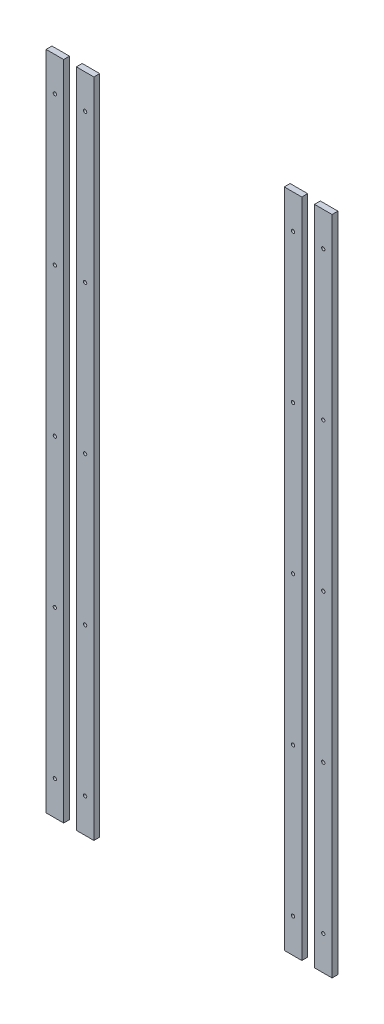
SolidWorks part; units mm, degrees
ref_plane "Спереди" through (0, 0, 0) normal (0, 0, 1) x (1, 0, 0)
ref_plane "Сверху" through (0, 0, 0) normal (0, 1, 0) x (1, 0, 0)
ref_plane "Справа" through (0, 0, 0) normal (1, 0, 0) x (0, 0, -1)
sketch "Четыре_направляющие_эскиз" plane through (0, 0, 0) normal (0, 0, 1) x (1, 0, 0)
  line L0 (325.5, -435) -> (343.5, -435)
  line L1 (343.5, -435) -> (343.5, 243)
  line L2 (343.5, 243) -> (325.5, 243)
  line L3 (325.5, 243) -> (325.5, -435)
  line L4 (356.5, -435) -> (374.5, -435)
  line L5 (374.5, -435) -> (374.5, 243)
  line L6 (374.5, 243) -> (356.5, 243)
  line L7 (356.5, 243) -> (356.5, -435)
  line L8 (569.7, -435) -> (587.7, -435)
  line L9 (587.7, -435) -> (587.7, 243)
  line L10 (587.7, 243) -> (569.7, 243)
  line L11 (569.7, 243) -> (569.7, -435)
  line L12 (600.7, -435) -> (618.7, -435)
  line L13 (618.7, -435) -> (618.7, 243)
  line L14 (618.7, 243) -> (600.7, 243)
  line L15 (600.7, 243) -> (600.7, -435)
  dimension "X001" = 325.5
  dimension "X002" = 343.5
  dimension "X003" = 356.5
  dimension "X004" = 374.5
  dimension "X005" = 569.7
  dimension "X006" = 587.7
  dimension "X007" = 600.7
  dimension "X008" = 618.7
  dimension "Y001" = 435
  dimension "Y002" = 243
extrude "Четыре_направляющие_6мм" add sketch "Четыре_направляющие_эскиз" along normal blind 6
sketch "Крепление_направляющих_М3_эскиз" plane through (0, 0, 0) normal (0, 0, 1) x (1, 0, 0)
  circle A0 centre (334.5, -400) radius 1.7
  circle A1 centre (365.5, -400) radius 1.7
  circle A2 centre (578.7, -400) radius 1.7
  circle A3 centre (609.7, -400) radius 1.7
  dimension "Диаметр001" = 3.4
  dimension "Диаметр002" = 3.4
  dimension "Диаметр003" = 3.4
  dimension "Диаметр004" = 3.4
  dimension "X001" = 334.5
  dimension "X002" = 365.5
  dimension "X003" = 578.7
  dimension "X004" = 609.7
  dimension "Y001" = 400
extrude "Проходы_направляющих_М3" cut sketch "Крепление_направляющих_М3_эскиз" against normal through all and the other way through all
pattern_linear "Массив_крепления_направляющих_5рядов" count 5 spacing 152 along (0, 1, 0) of "Проходы_направляющих_М3"
equation "\"Толщина стенки\" = \"Толщина тонких панелей\""
equation "\"Ширина груза\"= 160"
equation "\"Глубина груза\"= 240"
equation "\"Высота груза\"= 160"
equation "\"Ширина ячейки\"= \"Ширина груза\" + 10"
equation "\"Глубина ячейки\"= \"Глубина груза\" + 10"
equation "\"Высота ячейки\"= \"Высота груза\" + 10 + 13"
equation "\"Колво ячеек ширина\"= 2"
equation "\"Колво ячеек высота\"= 2"
equation "\"Крепление дверцы\"= 5 "
equation "\"Ширина рейки\"= \"Толщина шестерни\""
equation "\"Высота рейки\"= 20"
equation "\"Высота пола\" = 2*\"Толщина тонких панелей\""
equation "\"Колво полозьев\"= 5"
equation "\"Отступ рейки\"= 20"
equation "\"Глубина каретки\"= \"Глубина ячейки\" + 30 + \"Мотор Y высота корпуса\" + 20 + \"Удлинение платформы по глубине\""
equation "\"Длинна рейки\" = (\"Ширина ячейки\"+\"Толщина вертикальных стенок\"+\"Крепление дверцы\")*\"Колво ячеек ширина\"+\"Ширина ячейки выгрузки\"*\"Колво выгрузки\"+\"Толщина вертикальных стенок\"+2*\"Отступ крепления мотора фиксации\"-\"Крепление дверцы\"*\"Колво ячеек ширина\""
equation "\"Отступ шпильки\"= 26"
equation "\"Диаметр шпильки\"= 5"
equation "\"Длинна шпильки\" = (\"Высота ячейки\"+\"Толщина горизонтальных плит\"+\"Высота пола\")*\"Колво ячеек высота\"+2*(\"Толщина горизонтальных плит\"+\"Отступ рейки\")"
equation "\"Ширина пластины\" = 50"
equation "\"Высота зона выгрузки\"= \"Высота ячейки\" * 2 + \"Толщина стенки\" * 2"
equation "\"Колво выгрузки\"= 1"
equation "\"Ширина ячейки выгрузки\" = \"Ширина ячейки\"+\"Толщина вертикальных стенок\"+2*\"Отступ крепления мотора фиксации\""
equation "\"Отступ крепления мотора фиксации\" = (70-\"Толщина вертикальных стенок\")/2"
equation "\"Мотор X ширина корпуса\"= 42.3"
equation "\"Мотор X высота корпуса\"= 42.3"
equation "\"Мотор X длина корпуса\"= 40"
equation "\"Мотор X вылет вала\"= 19.8"
equation "\"Мотор Y ширина корпуса\"= 42.3"
equation "\"Мотор Y высота корпуса\"= 42.3"
equation "\"Мотор Y длина корпуса\"= 48"
equation "\"Мотор Y вылет вала\"= 30"
equation "\"Мотор Z ширина корпуса\"= 42"
equation "\"Мотор Z высота корпуса\"= 42"
equation "\"Мотор Z длина корпуса\"= 40"
equation "\"Мотор Z вылет вала\"= 23"
equation "\"Мотор диаметр вала ПРЕДВ\"= 5"
equation "\"Мотор шаг крепления ПРЕДВ\"= 31"
equation "\"Мотор диаметр отверстий ПРЕДВ\"= 3"
equation "\"Мотор глубина отверстий ПРЕДВ\"= 4.5"
equation "\"Мотор диаметр буртика ПРЕДВ\"= 22"
equation "\"Мотор высота буртика ПРЕДВ\"= 2"
equation "\"Мотор диаметр шкива ПРЕДВ\"= 16"
equation "\"Мотор длина шкива ПРЕДВ\"= 12"
equation "\"Мотор отступ шкива ПРЕДВ\"= 5"
equation "\"Мотор X шаг градусов\"= 1.8"
equation "\"Мотор Y шаг градусов\"= 1.8"
equation "\"Мотор Z шаг градусов\"= 1.8"
equation "\"Мотор Y диаметр ротора\"= 25.78"
equation "\"Толщина шестерни\"= 10"
equation "\"Толщина тонких панелей\" = 6"
equation "\"Толщина вертикальных стенок\" = 6"
equation "\"Толщина горизонтальных плит\" = 6"
equation "\"Базовая высота корпуса\"= (\"Высота ячейки\"+\"Толщина тонких панелей\"+\"Высота пола\")*\"Колво ячеек высота\"+6*\"Толщина тонких панелей\"+\"Мотор X ширина корпуса\"+\"Мотор Y ширина корпуса\"+75"
equation "\"Высота корпуса\"= (\"Высота ячейки\"+\"Толщина горизонтальных плит\"+\"Высота пола\")*\"Колво ячеек высота\"+2*\"Толщина горизонтальных плит\"+4*\"Толщина тонких панелей\"+\"Мотор X ширина корпуса\"+\"Мотор Y ширина корпуса\"+75"
equation "\"Смещение центра корпуса\"= (\"Высота корпуса\"-\"Базовая высота корпуса\")/2-(\"Толщина горизонтальных плит\"-\"Толщина тонких панелей\")"
equation "\"Отметка пола\"= -\"Базовая высота корпуса\"/2+\"Толщина тонких панелей\""
equation "\"Отметка потолка\"= \"Отметка пола\"+\"Высота корпуса\"-2*\"Толщина горизонтальных плит\""
equation "\"Отметка верхней полки\"= \"Отметка потолка\"-(28+\"Толщина тонких панелей\")-\"Высота ячейки\"-\"Высота пола\""
equation "\"Отметка нижней полки\"= \"Отметка верхней полки\"-\"Высота ячейки\"-\"Высота пола\"-\"Толщина горизонтальных плит\""
equation "\"Ширина направляющей\"= 18"
equation "\"X001@Четыре_направляющие_эскиз\" = \"Глубина ячейки\"+74.5-9+\"Смещение дальнего ряда под симметрию\""
equation "\"X002@Четыре_направляющие_эскиз\" = \"Глубина ячейки\"+74.5+9+\"Смещение дальнего ряда под симметрию\""
equation "\"X003@Четыре_направляющие_эскиз\" = \"Глубина ячейки\"+105.5-9+\"Смещение дальнего ряда под симметрию\""
equation "\"X004@Четыре_направляющие_эскиз\" = \"Глубина ячейки\"+105.5+9+\"Смещение дальнего ряда под симметрию\""
equation "\"X005@Четыре_направляющие_эскиз\" = (2*\"Глубина ячейки\"+46.8-9-\"Смещение пары направляющих от рейки\")+\"Удлинение платформы по глубине\""
equation "\"X006@Четыре_направляющие_эскиз\" = (2*\"Глубина ячейки\"+46.8+9-\"Смещение пары направляющих от рейки\")+\"Удлинение платформы по глубине\""
equation "\"X007@Четыре_направляющие_эскиз\" = (2*\"Глубина ячейки\"+77.8-9-\"Смещение пары направляющих от рейки\")+\"Удлинение платформы по глубине\""
equation "\"X008@Четыре_направляющие_эскиз\" = (2*\"Глубина ячейки\"+77.8+9-\"Смещение пары направляющих от рейки\")+\"Удлинение платформы по глубине\""
equation "\"Y001@Четыре_направляющие_эскиз\" = 2*\"Ширина ячейки\"+87+\"Расширение корпуса на сторону\"-2"
equation "\"Y002@Четыре_направляющие_эскиз\" = \"Ширина ячейки\"+65+\"Расширение корпуса на сторону\"-2"
equation "\"D1@Четыре_направляющие_6мм\" = \"Толщина тонких панелей\""
equation "\"X001@Крепление_направляющих_М3_эскиз\" = \"Глубина ячейки\"+74.5+\"Смещение дальнего ряда под симметрию\""
equation "\"X002@Крепление_направляющих_М3_эскиз\" = \"Глубина ячейки\"+105.5+\"Смещение дальнего ряда под симметрию\""
equation "\"X003@Крепление_направляющих_М3_эскиз\" = (2*\"Глубина ячейки\"+46.8-\"Смещение пары направляющих от рейки\")+\"Удлинение платформы по глубине\""
equation "\"X004@Крепление_направляющих_М3_эскиз\" = (2*\"Глубина ячейки\"+77.8-\"Смещение пары направляющих от рейки\")+\"Удлинение платформы по глубине\""
equation "\"Y001@Крепление_направляющих_М3_эскиз\" = (2*\"Ширина ячейки\"+87+\"Расширение корпуса на сторону\"-2)-35"
equation "\"Диаметр001@Крепление_направляющих_М3_эскиз\" = 3.4"
equation "\"Диаметр002@Крепление_направляющих_М3_эскиз\" = 3.4"
equation "\"Диаметр003@Крепление_направляющих_М3_эскиз\" = 3.4"
equation "\"Диаметр004@Крепление_направляющих_М3_эскиз\" = 3.4"
equation "\"D3@Массив_крепления_направляющих_5рядов\" = ((2*\"Ширина ячейки\"+87+\"Расширение корпуса на сторону\"-2)+(\"Ширина ячейки\"+65+\"Расширение корпуса на сторону\"-2)-70)/4"
equation "\"Смещение пары направляющих от рейки\"= 10"
equation "\"Расширение корпуса на сторону\"= 10+(\"Ширина пластины\"-50)"
equation "\"Смещение дальнего ряда под симметрию\"= \"Смещение пары направляющих от рейки\""
equation "\"Переднее удлинение полозьев\"= 16.2"
equation "\"Зазор полозьев от задней стенки\"= 10"
equation "\"Удлинение платформы по глубине\"= \"Переднее удлинение полозьев\"+\"Зазор полозьев от задней стенки\"+15.7"
equation "\"Зазор между основанием и рейкой\"= 5"
